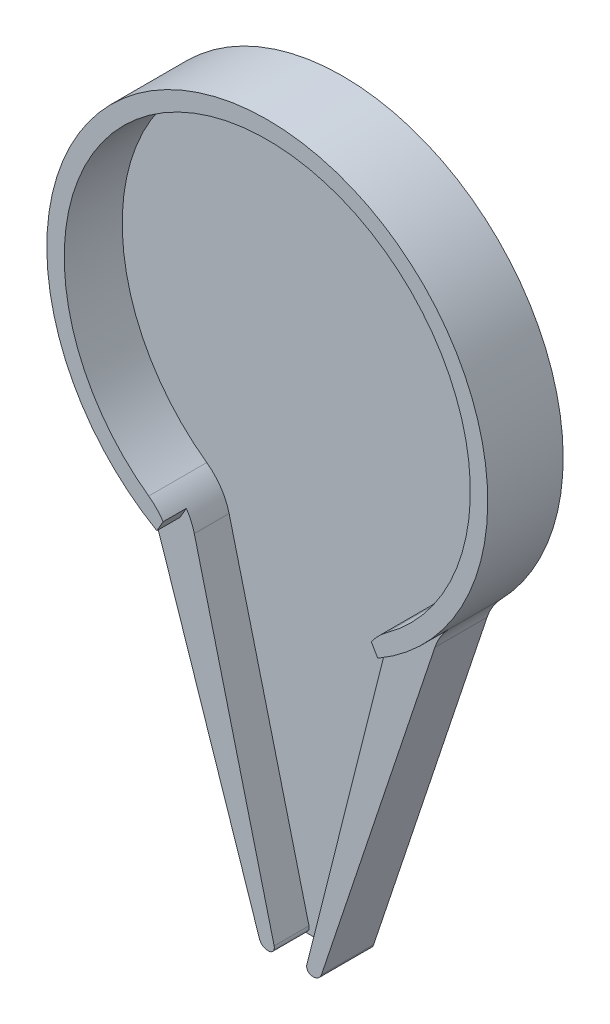
SolidWorks part; units mm, degrees
ref_plane "Plan de face" through (0, 0, 0) normal (0, 0, 1) x (1, 0, 0)
ref_plane "Plan de dessus" through (0, 0, 0) normal (0, 1, 0) x (1, 0, 0)
ref_plane "Plan de droite" through (0, 0, 0) normal (1, 0, 0) x (0, 0, -1)
sketch "Esquisse1" plane through (0, 0, 0) normal (0, 0, 1) x (1, 0, 0)
  circle A0 centre (0, 0) radius 38
  circle A1 centre (0, 0) radius 35
  dimension "D1" = 3
  dimension "D2" = 70
extrude "Boss.-Extru.1" add sketch "Esquisse1" along normal blind 10
sketch "Esquisse2" plane through (0, 0, 0) normal (0, 0, -1) x (-1, 0, 0)
  circle A0 centre (0, 0) radius 38 construction
  circle A1 centre (0, 0) radius 38
extrude "Boss.-Extru.2" add sketch "Esquisse2" along normal blind 3
sketch "Esquisse3" plane through (0, 0, 0) normal (0, 0, 1) x (1, 0, 0)
  line L0 (-35, 0) -> (-5, -90) construction
  line L1 (-5, -90) -> (5, -90)
  line L2 (0, -90) -> (0, 0) construction
  line L3 (0, 0) -> (-35, 0) construction
  line L4 (-5, -90) -> (-25.6562, -28.0314)
  line L5 (-25.6562, -28.0314) -> (25.6562, -28.0314)
  line L6 (5, -90) -> (25.6562, -28.0314)
  circle A0 centre (0, 0) radius 35 construction
  circle A1 centre (0, 0) radius 35 construction
  circle A2 centre (0, 0) radius 38 construction
  point P6 (0, 0)
  point P15 (0, -28.0314)
  dimension "D1" = 5
  dimension "D2" = 90
extrude "Boss.-Extru.3" add sketch "Esquisse3" against normal blind 3
sketch "Esquisse4" plane through (0, 0, 0) normal (0, 0, 1) x (1, 0, 0)
  line L0 (0, -90) -> (0, 0) construction
  line L1 (-5, -90) -> (5, -90) construction
  line L2 (-19.0376, -32.8872) -> (-17.5346, -30.2909)
  line L3 (-17.5346, -30.2909) -> (0, 0) construction
  line L4 (-17.5346, -30.2909) -> (17.5346, -30.2909)
  line L5 (-19.0376, -32.8872) -> (0, -90)
  line L6 (19.0376, -32.8872) -> (0, -90)
  line L7 (19.0376, -32.8872) -> (17.5346, -30.2909)
  line L9 (-25.6562, -28.0314) -> (-5, -90) construction
  circle A0 centre (0, 0) radius 35 construction
  arc A1 (-25.6562, -28.0314) -> (25.6562, -28.0314) centre (0, 0) ccw construction
  point P10 (0, -79.1184)
  point P11 (-17.7047, -33.6236)
  point P14 (0, -30.2909)
extrude "Enlèv. mat.-Extru.1" cut sketch "Esquisse4" along normal through all
sketch "Esquisse5" plane through (0, 0, 0) normal (0, 0, 1) x (1, 0, 0)
  line L0 (-5, -90) -> (-25.6562, -28.0314)
  line L1 (-25.6562, -28.0314) -> (-17.5346, -30.2909)
  line L2 (-17.5346, -30.2909) -> (-2.5, -90)
  line L3 (-5, -90) -> (5, -90) construction
  line L4 (-2.5, -90) -> (-5, -90)
  line L5 (0, -90) -> (0, -68.4348) construction
  line L6 (2.5, -90) -> (5, -90)
  line L7 (17.5346, -30.2909) -> (2.5, -90)
  line L8 (25.6562, -28.0314) -> (17.5346, -30.2909)
  line L9 (5, -90) -> (25.6562, -28.0314)
  dimension "D1" = 5
extrude "Boss.-Extru.4" add sketch "Esquisse5" along normal blind 6
fillet "Congé1" radius 10 4 edges at (25.6562, -28.0314, 1.5) (-25.6562, -28.0314, 1.5) (17.5346, -30.2909, 3) (-17.5346, -30.2909, 3) tangent propagation no
fillet "Congé3" radius 1 2 edges at (2.5, -90, 3) (-2.5, -90, 3)
fillet "Congé4" radius 1.5 2 edges at (5, -90, 1.5) (-5, -90, 1.5)
